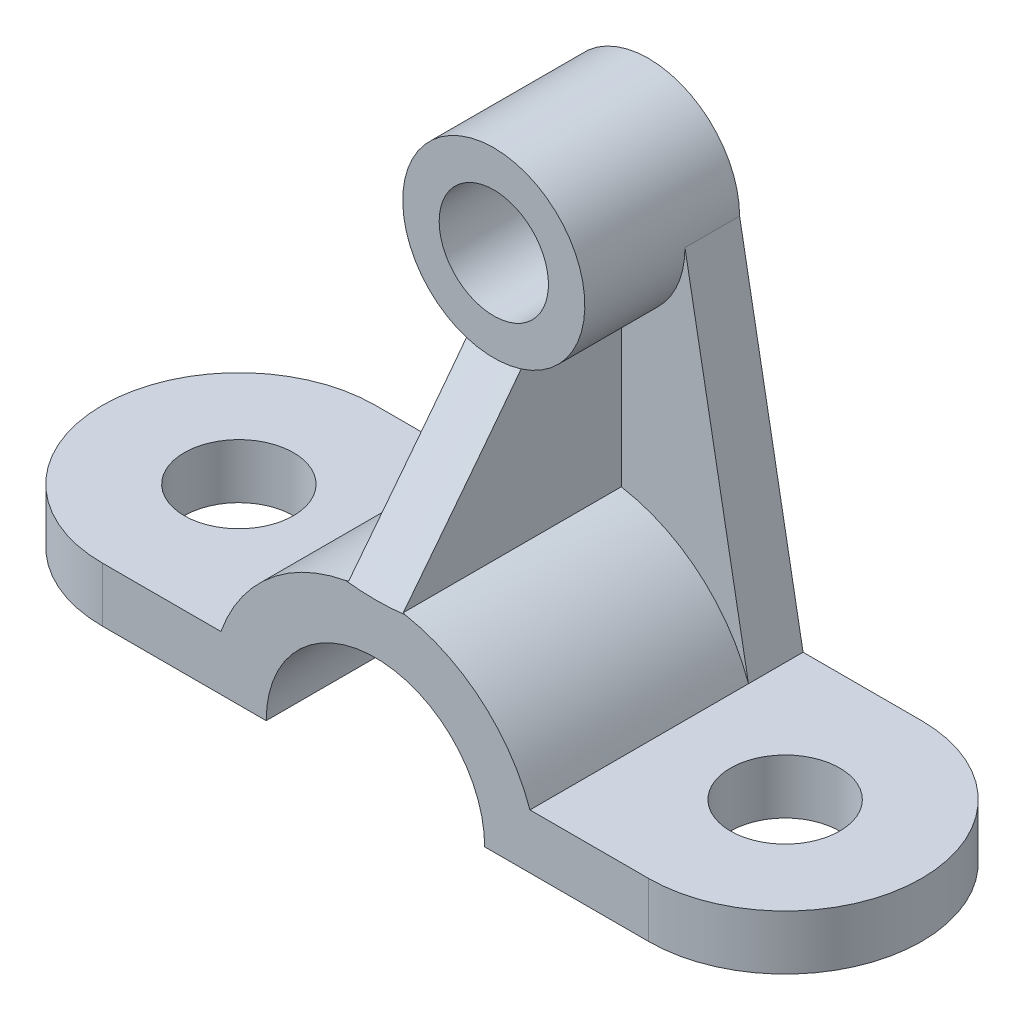
SolidWorks part; units mm, degrees
ref_plane "Front Plane" through (0, 0, 0) normal (0, 0, 1) x (1, 0, 0)
ref_plane "Top Plane" through (0, 0, 0) normal (0, 1, 0) x (1, 0, 0)
ref_plane "Right Plane" through (0, 0, 0) normal (1, 0, 0) x (0, 0, -1)
sketch "Sketch1" plane through (0, 0, 0) normal (0, 1, 0) x (1, 0, 0)
  line L1 (0, -30) -> (60, -30)
  line L2 (0, -30) -> (-60, -30)
  line L3 (0, 30) -> (60, 30)
  line L4 (0, 30) -> (-60, 30)
  arc A0 (-60, 30) -> (-60, -30) centre (-60, 0) ccw
  arc A1 (60, 30) -> (60, -30) centre (60, 0) cw
  circle A2 centre (-60, 0) radius 12
  circle A3 centre (60, 0) radius 12
extrude "Boss-Extrude1" add sketch "Sketch1" along normal blind 12
sketch "Sketch2" plane through (0, 0, 30) normal (0, 0, 1) x (1, 0, 0)
  line L0 (-24, 0) -> (24, 0)
  line L1 (-33.9411, 12) -> (-20.7846, 12)
  line L2 (-60, 0) -> (60, 0) construction
  line L3 (33.9411, 12) -> (20.7846, 12)
  line L4 (-60, 12) -> (60, 12) construction
  arc A0 (24, 0) -> (-24, 0) centre (0, 0) ccw
  arc A1 (33.9411, 12) -> (-33.9411, 12) centre (0, 0) ccw
  point P12 (0, 0)
  point P14 (0, 0)
  line M8 (-60, 0) -> (60, 0)
  line M10 (60, 12) -> (-60, 12)
extrude "Boss-Extrude2" add sketch "Sketch2" against normal blind 60 contours A1 A0 M10 region at (0, 24.0702, 30)
extrude "Cut-Extrude2" cut sketch "Sketch2<7>" against normal blind 60 contours A0 M8 M10 | A0 M10 region at (0, 5.862, 30) region at (0, 16.9205, 30)
sketch "Sketch2<7>" plane through (0, 0, 30) normal (0, 0, 1) x (1, 0, 0) same geometry as "Sketch2"
sketch "Sketch3" plane through (0, 0, -30) normal (0, 0, -1) x (-1, 0, 0)
  line L1 (-33.9411, 12) -> (-20, 88)
  line L2 (33.9411, 12) -> (20, 88)
  circle A0 centre (0, 88) radius 12
  circle A1 centre (0, 88) radius 20
  arc A2 (-33.9411, 12) -> (33.9411, 12) centre (0, 0) cw
  arc M8 (33.9411, 12) -> (-33.9411, 12) centre (0, 0) ccw
extrude "Boss-Extrude4" add sketch "Sketch3" against normal blind 12 contours A1 L1 L2 M8 region at (0, 50.6006, -30)
extrude "Boss-Extrude5" add sketch "Sketch3<4>" against normal blind 34 contours A1 A0 region at (0, 107.4343, -30)
sketch "Sketch3<4>" plane through (0, 0, -30) normal (0, 0, -1) x (-1, 0, 0) same geometry as "Sketch3"
sketch "Sketch5" plane through (0, 0, -18) normal (0, 0, 1) x (1, 0, 0)
  line L1 (-6, 35.4965) -> (-6, 68.9212)
  line L2 (6, 68.9212) -> (6, 35.4965)
  arc A1 (33.9411, 12) -> (-33.9411, 12) centre (0, 0) ccw construction
  arc A2 (33.9411, 12) -> (-33.9411, 12) centre (0, 0) ccw construction
  arc A3 (-6, 35.4965) -> (6, 35.4965) centre (0, 0) cw
  circle A4 centre (0, 88) radius 20 construction
  arc A5 (-6, 68.9212) -> (6, 68.9212) centre (0, 88) ccw
extrude "Boss-Extrude7" add sketch "Sketch5" along normal blind 48
chamfer "Chamfer1" distance 26 distance2 33 1 edges at (0, 68, 30) first distance on face at (0, 68.4606, 17)
